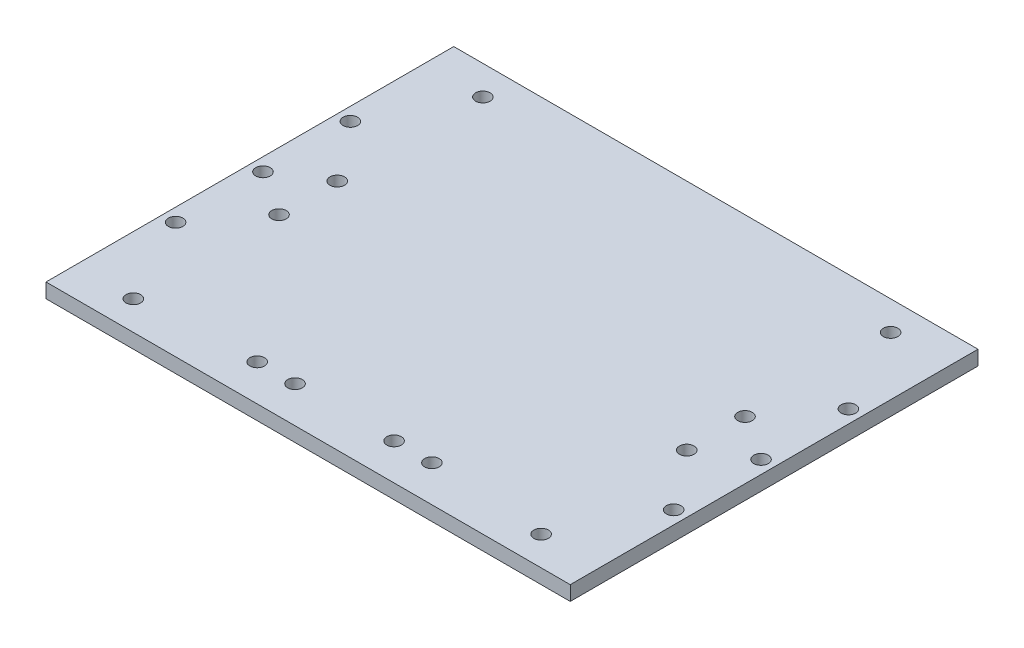
SolidWorks part; units mm, degrees
ref_plane "Front Plane" through (0, 0, 0) normal (0, 0, 1) x (1, 0, 0)
ref_plane "Top Plane" through (0, 0, 0) normal (0, 1, 0) x (1, 0, 0)
ref_plane "Right Plane" through (0, 0, 0) normal (1, 0, 0) x (0, 0, -1)
sketch "Sketch2" plane through (0, 0, 0) normal (0, 1, 0) x (1, 0, 0)
  line L0 (0, 88.9) -> (0, -88.9) construction
  line L1 (-114.3, -88.9) -> (114.3, -88.9)
  line L2 (-114.3, -88.9) -> (-114.3, 88.9)
  line L3 (-114.3, 88.9) -> (114.3, 88.9)
  line L4 (114.3, -88.9) -> (114.3, 88.9)
  line L5 (-114.3, 0) -> (114.3, 0) construction
  circle A11 centre (-21.59, -73.025) radius 3.175
  circle A12 centre (-108.585, 0) radius 3.175
  circle A13 centre (-108.585, -38.1) radius 3.175
  circle A14 centre (-108.585, 38.1) radius 3.175
  circle A15 centre (108.585, -38.1) radius 3.175
  circle A16 centre (108.585, 0) radius 3.175
  circle A17 centre (108.585, 38.1) radius 3.175
  circle A18 centre (-38.1, -73.025) radius 3.175
  circle A19 centre (38.1, -73.025) radius 3.175
  circle A20 centre (21.59, -73.025) radius 3.175
  circle A21 centre (88.9, -76.2) radius 3.175
  circle A22 centre (88.9, -12.7) radius 3.175
  circle A23 centre (88.9, 76.2) radius 3.175
  circle A24 centre (88.9, 12.7) radius 3.175
  circle A25 centre (-88.9, 76.2) radius 3.175
  circle A26 centre (-88.9, 12.7) radius 3.175
  circle A27 centre (-88.9, -12.7) radius 3.175
  circle A28 centre (-88.9, -76.2) radius 3.175
  dimension "D7" = 63.5
  dimension "D8" = 25.4
  dimension "D9" = 12.7
  dimension "D11" = 21.59
  dimension "D14" = 6.35
  dimension "D15" = 15.875
  dimension "D16" = 6.35
  dimension "D17" = 5.715
  dimension "D18" = 6.35
  dimension "D19" = 38.1
  dimension "D20" = 38.1
  dimension "D21" = 6.35
  dimension "D12" = 6.35
  dimension "D5" = 6.35
  dimension "D6" = 6.35
  dimension "D1" = 88.9
  dimension "D2" = 177.8
  dimension "D3" = 228.6
  dimension "D4" = 114.3
  dimension "D13" = 38.1
extrude "Boss-Extrude1" add sketch "Sketch2" along normal blind 6.35
